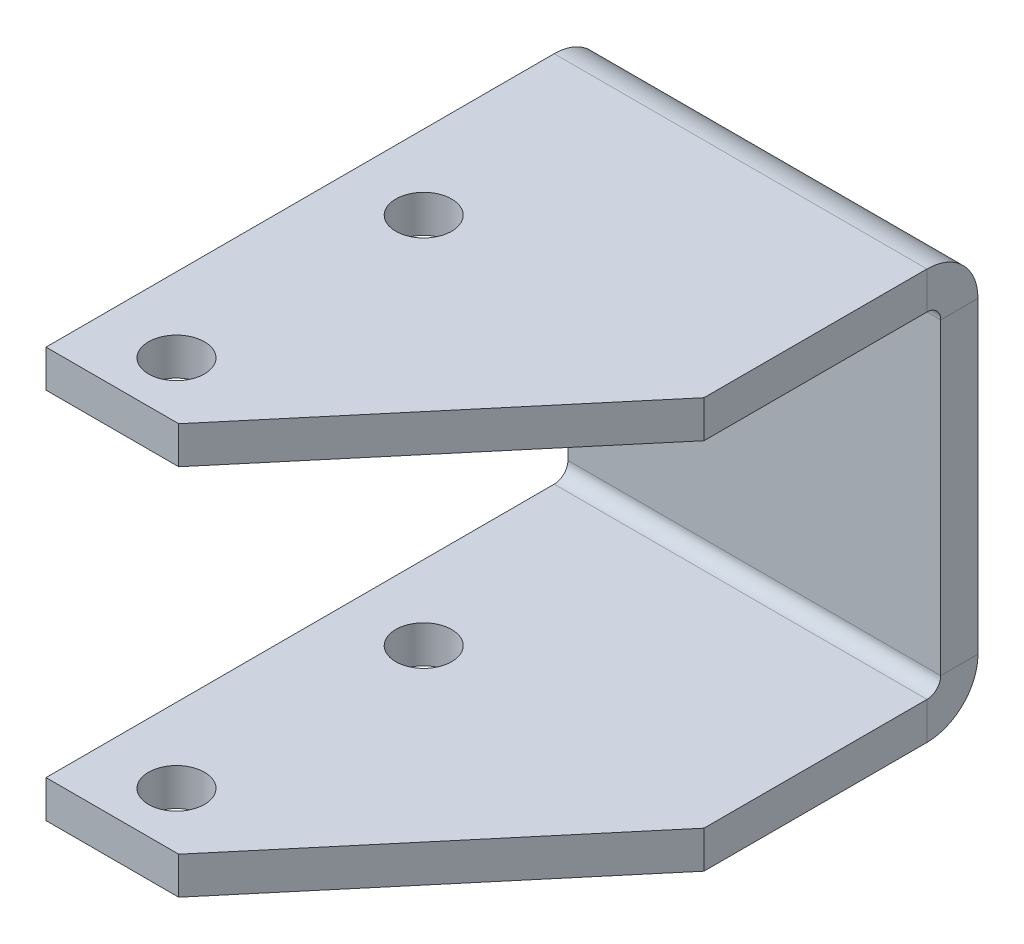
SolidWorks part; units mm, degrees
note: The reader was unsure of these and kept them because the rebuilt part matched: flange length of "Bordo-Flangia3".
ref_plane "Piano frontale" through (0, 0, 0) normal (0, 0, 1) x (1, 0, 0)
ref_plane "Piano superiore" through (0, 0, 0) normal (0, 1, 0) x (1, 0, 0)
ref_plane "Piano destro" through (0, 0, 0) normal (1, 0, 0) x (0, 0, -1)
sketch "Schizzo1" plane through (0, 0, 0) normal (0, 0, 1) x (1, 0, 0)
  line L0 (0, 18) -> (0, 0)
  line L1 (0, 0) -> (20, 0)
  line L2 (20, 0) -> (20, 18)
  line L3 (20, 18) -> (0, 18)
  dimension "D1" = 20
  dimension "D2" = 18
base flange "Base-Flangia1" sketch "Schizzo1" thickness 2 reverse thickness direction no parameters "D1"=0.7366
edge flange "Bordo-Flangia3" sketch "Schizzo17" flange profiles "Schizzo17", "Schizzo18" flange angle 90 flange length 30 flange position material outside bend radius 0.7366 thickness 2 relief rectangular parameters "D6"=10, "D8"=1
sketch "Schizzo17" plane through (0, 18, 0) normal (0, -1, 0) x (1, 0, 0)
  line L2 (20, 0) -> (20, 28)
  line L3 (20, 28) -> (0, 28)
  line L4 (0, 28) -> (0, 0)
  line L9 (0, 0) -> (20, 0) construction
  line L10 (0, 0) -> (20, 0)
sketch "Schizzo18" plane through (0, 0, 0) normal (0, 1, 0) x (-1, 0, 0)
  line L2 (0, 0) -> (0, 28)
  line L3 (0, 28) -> (-20, 28)
  line L4 (-20, 28) -> (-20, 0)
  line L9 (-20, 0) -> (0, 0) construction
  line L10 (-20, 0) -> (0, 0)
bend "PiegaturaBordo3" bend radius 0.7366 bend angle 90 parameters "D5"=1
bend "PiegaturaBordo4" bend radius 0.7366 bend angle 90 parameters "D5"=2
sketch "Schizzo19" plane through (0, -2, 0) normal (0, -1, 0) x (1, 0, 0)
  line L0 (0, 28) -> (20, 28) construction
  line L1 (20, 28) -> (0, 28) construction
  line L2 (7.1194, 28) -> (20, 12.7)
  line L3 (20, 0.7366) -> (20, 28) construction
  line L4 (7.1194, 28) -> (20, 28)
  line L5 (20, 28) -> (20, 12.7)
  line L6 (20, 28) -> (20, 0.7366) construction
  dimension "D1" = 15.3
  dimension "D2" = 20
extrude "Taglio-Estrusione1" cut sketch "Schizzo19" against normal through all both and the other way through all normal cut yes
sketch "Schizzo20" plane through (0, 20, 0) normal (0, 1, 0) x (1, 0, 0)
  line L0 (0, -0.7366) -> (20, -0.7366) construction
  line L1 (0, -28) -> (0, -0.7366) construction
  line L2 (7.1194, -28) -> (0, -28) construction
  circle A0 centre (4, -11.7366) radius 1.5
  circle A1 centre (4, -25) radius 1.5
  dimension "D1" = 3
  dimension "D4" = 3
  dimension "D2" = 11
  dimension "D3" = 4
  dimension "D5" = 3
  dimension "D6" = 4
extrude "Taglio-Estrusione2" cut sketch "Schizzo20" against normal through all both and the other way through all normal cut yes
sketch "Linee di piegatura1" [suppressed] plane through (0, 0, 0) normal (0, 1, 0) x (1, 0, 0)
sketch "Casella di contorno1" [suppressed] plane through (0, 0, 0) normal (0, 1, 0) x (1, 0, 0)
sheet metal parameters "Lamiera1" thickness 2 parameters "D1"=0.7366
flat pattern "Ripetizione piatta1" [suppressed]
sketch "Linee di piegatura2" plane through (0, 0, 0) normal (0, 1, 0) x (1, 0, 0)
sketch3d "Casella di contorno2" [suppressed]
  line L0 (0, 0, 0) -> (20, 0, 0) construction
  line L1 (0, 15, 0) -> (20, 15, 0) construction
  line L2 (0, 0, 0) -> (0, 15, 0) construction
  line L3 (20, 0, 0) -> (20, 15, 0) construction
sheet metal parameters "Lamiera4" thickness 2 parameters "D1"=0.7366
flat pattern "Ripetizione piatta1"
sketch "Linee di piegatura2" plane through (0, 0, 0) normal (0, 0, 1) x (1, 0, 0)
  line L0 (0, -0.3132) -> (20, -0.3132) construction
  line L1 (20, 15.3132) -> (0, 15.3132) construction
  line L2 (0, -0.3132) -> (20, -0.3132) construction
  line L3 (20, 15.3132) -> (0, 15.3132) construction
sketch3d "Casella di contorno2" [suppressed]
  line L0 (20, 43.6263, 0) -> (20, -28.6263, 0) construction
  line L1 (0, 43.6263, 0) -> (0, -28.6263, 0) construction
  line L2 (20, 43.6263, 0) -> (0, 43.6263, 0) construction
  line L3 (20, -28.6263, 0) -> (0, -28.6263, 0) construction
bend of the flat pattern "Appiattito-<PiegaturaBordo3>1"
bend of the flat pattern "Appiattito-<PiegaturaBordo4>1"
sheet metal parameters "Lamiera5" thickness 2 parameters "D1"=0.7366
flat pattern "Ripetizione piatta1"
sketch "Linee di piegatura2" plane through (0, 0, 0) normal (0, 0, 1) x (1, 0, 0)
  line L0 (0, -0.3132) -> (20, -0.3132) construction
  line L1 (20, 15.3132) -> (0, 15.3132) construction
  line L2 (0, -0.3132) -> (20, -0.3132) construction
  line L3 (20, 15.3132) -> (0, 15.3132) construction
sketch3d "Casella di contorno2" [suppressed]
  line L0 (20, 43.6263, 0) -> (20, -28.6263, 0) construction
  line L1 (0, 43.6263, 0) -> (0, -28.6263, 0) construction
  line L2 (20, 43.6263, 0) -> (0, 43.6263, 0) construction
  line L3 (20, -28.6263, 0) -> (0, -28.6263, 0) construction
bend of the flat pattern "Appiattito-<PiegaturaBordo3>1"
bend of the flat pattern "Appiattito-<PiegaturaBordo4>1"
sheet metal parameters "Lamiera9" thickness 2 parameters "D1"=0.7366
flat pattern "Ripetizione piatta1"
sketch "Linee di piegatura2" plane through (0, 0, 0) normal (0, 0, 1) x (1, 0, 0)
  line L0 (0, -0.3132) -> (20, -0.3132) construction
  line L1 (20, 18.3132) -> (0, 18.3132) construction
  line L2 (0, -0.3132) -> (20, -0.3132) construction
  line L3 (20, 18.3132) -> (0, 18.3132) construction
sketch3d "Casella di contorno2" [suppressed]
  line L0 (20, 46.6263, 0) -> (20, -28.6263, 0) construction
  line L1 (0, 46.6263, 0) -> (0, -28.6263, 0) construction
  line L2 (20, 46.6263, 0) -> (0, 46.6263, 0) construction
  line L3 (20, -28.6263, 0) -> (0, -28.6263, 0) construction
bend of the flat pattern "Appiattito-<PiegaturaBordo3>1"
bend of the flat pattern "Appiattito-<PiegaturaBordo4>1"
